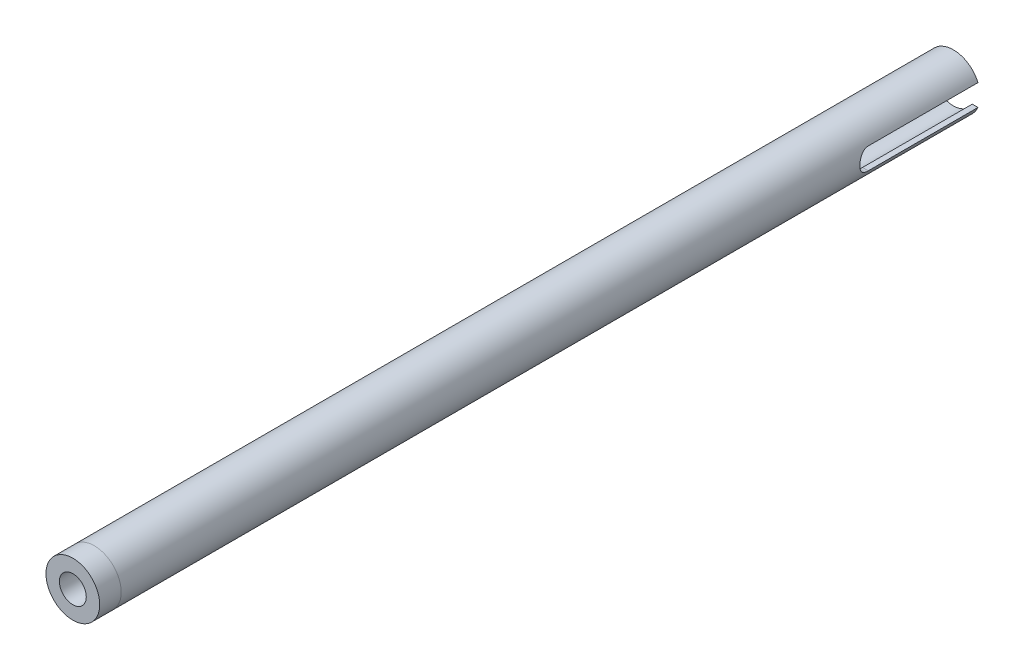
SolidWorks part; units mm, degrees
material "AISI 4130 Steel, annealed at 865C"
ref_plane "Front Plane" through (0, 0, 0) normal (0, 0, 1) x (1, 0, 0)
ref_plane "Top Plane" through (0, 0, 0) normal (0, 1, 0) x (1, 0, 0)
ref_plane "Right Plane" through (0, 0, 0) normal (1, 0, 0) x (0, 0, -1)
sketch "Axis" plane through (0, 0, 0) normal (0, 1, 0) x (1, 0, 0)
  line L0 (0, 0) -> (0, 260.0231) construction
  line L1 (0, 0) -> (0, -34.925) construction
  line L2 (0, 260.0231) -> (-7.9375, 260.0231) construction
  line L3 (0, 283.4513) -> (-10.3187, 252.9946) construction
  dimension "D1" = 34.925
  dimension "D2" = 7.9375
sketch "Sketch1" plane through (0, 0, 0) normal (0, 0, 1) x (1, 0, 0)
  line L0 (-7.9375, 0) -> (7.9375, 0) construction
  line L1 (-7.2748, 3.175) -> (7.2748, 3.175)
  line L2 (-7.2748, -3.175) -> (7.2748, -3.175)
  circle A0 centre (0, 0) radius 7.9375
  circle A1 centre (0, 0) radius 6.4135
  circle A2 centre (0, 0) radius 3.9688
  dimension "D1" = 15.875
  dimension "D3" = 7.9375
  dimension "D2" = 1.524
  dimension "D4" = 6.35
extrude "Threaded insert 1-1" add sketch "Sketch1" against normal blind 6.35 contours A2 L1 A1 | A1 L1 A0 | A2 L0 A1 L1 | A1 L0 A0 L1 | L0 A1 L2 A0 | L0 A2 L2 A1 | A2 L2 A1 | A1 L2 A0 | L0 A1 L2 A2 | L0 A0 L2 A1 | A0 L0 A1 L1 | A1 L0 A2 L1 region at (4.7887, 1.6543, 0) region at (4.7887, -1.6543, 0) region at (6.9234, 1.6163, 0) region at (6.9234, -1.6163, 0) region at (-4.7887, -1.6543, 0) region at (-4.7887, 1.6543, 0) region at (0, 4.6159, 0) region at (0, -4.6159, 0) region at (0, 6.5666, 0) region at (6.4237, -3.3281, 0) region at (-6.9234, -1.6163, 0) region at (-6.9234, 1.6163, 0)
extrude "Threaded insert 1-2" add sketch "Sketch1<3>" against normal blind 9.525 from surface contours A2 L1 A1 | A2 L0 A1 L1 | L0 A2 L2 A1 | A2 L2 A1 | L0 A1 L2 A2 | A1 L0 A2 L1 region at (4.7887, 1.6543, 0) region at (4.7887, -1.6543, 0) region at (-4.7887, -1.6543, 0) region at (-4.7887, 1.6543, 0) region at (0, 4.6159, 0) region at (0, -4.6159, 0) starting at face at (7.9375, 0, -6.35)
sketch "Sketch1<3>" plane through (0, 0, 0) normal (0, 0, 1) x (1, 0, 0) same geometry as "Sketch1"
extrude "A-arm tube" add sketch "Sketch1<4>" against normal up to vertex (260.0231 mm away) from surface separate body contours A1 L1 A0 | A1 L0 A0 L1 | L0 A1 L2 A0 | A1 L2 A0 | L0 A0 L2 A1 | A0 L0 A1 L1 region at (6.9234, 1.6163, 0) region at (6.9234, -1.6163, 0) region at (0, 6.5666, 0) region at (6.4237, -3.3281, 0) region at (-6.9234, -1.6163, 0) region at (-6.9234, 1.6163, 0) up to point (0, 0, -260.0231) starting at face at (6.4135, 0, -6.35)
sketch "Sketch1<4>" plane through (0, 0, 0) normal (0, 0, 1) x (1, 0, 0) same geometry as "Sketch1"
extrude "Apex slot" cut sketch "Sketch1<5>" along normal blind 35.56 from surface contours A0 L0 A1 L1 | L0 A0 L2 A1 | A1 L0 A0 L1 | L0 A1 L2 A0 region at (6.9234, 1.6163, 0) region at (6.9234, -1.6163, 0) region at (-6.9234, -1.6163, 0) region at (-6.9234, 1.6163, 0) starting at face at (6.4135, 0, -260.0231)
sketch "Sketch1<5>" plane through (0, 0, 0) normal (0, 0, 1) x (1, 0, 0) same geometry as "Sketch1"
fillet "Fillet1" radius 3.175 4 edges at (-6.4237, 3.175, -224.4631) (-6.4237, -3.175, -224.4631) (6.4237, -3.175, -224.4631) (6.4237, 3.175, -224.4631)
equation "\"tube diameter\"= 5 / 8"
equation "\"tube thickness\"= .06"
equation "\"apex thickness\"= .25"
equation "\"tube slot\"= 1.4"
equation "\"D1@Sketch1\"=\"tube diameter\""
equation "\"D2@Sketch1\"=\"tube thickness\""
equation "\"threaded insert hole\"= .3125"
equation "\"D3@Sketch1\"=\"threaded insert hole\""
equation "\"D4@Sketch1\"=\"apex thickness\""
equation "\"D1@Apex slot\" = \"tube slot\""
equation "\"D1@Fillet1\"=\"apex thickness\"/2"
